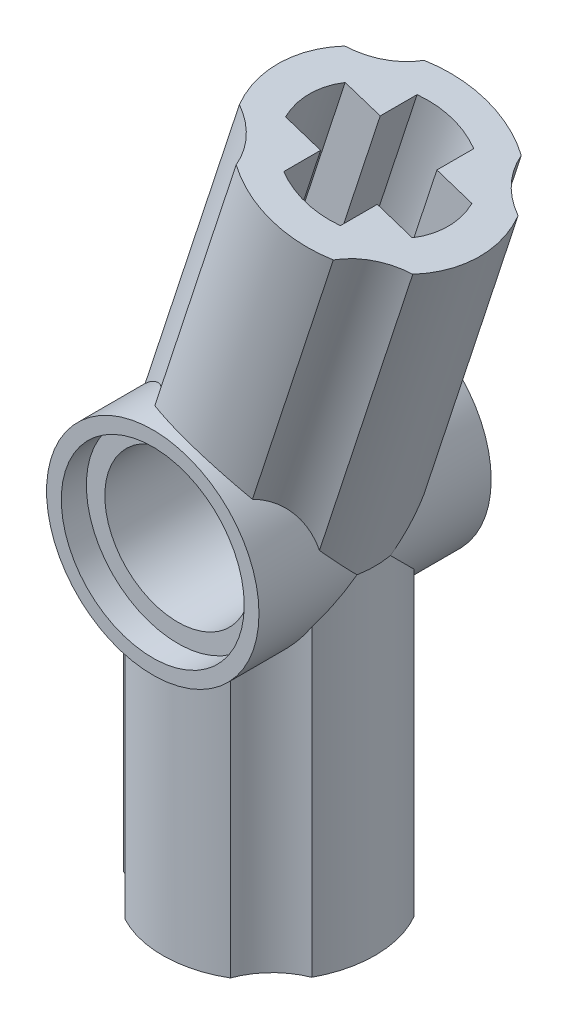
SolidWorks part; units mm, degrees
ref_plane "Front Plane" through (0, 0, 0) normal (0, 0, 1) x (1, 0, 0)
ref_plane "Top Plane" through (0, 0, 0) normal (0, 1, 0) x (1, 0, 0)
ref_plane "Right Plane" through (0, 0, 0) normal (1, 0, 0) x (0, 0, -1)
sketch "Croquis1" plane through (0, 0, 0) normal (0, 0, 1) x (1, 0, 0)
  circle A0 centre (0, 0) radius 3.1
  circle A1 centre (0, 0) radius 3.6
  circle A2 centre (0, 0) radius 2.475
  dimension "D1" = 4.95
  dimension "D2" = 6.2
  dimension "D3" = 7.2
extrude "Saliente-Extruir1" add sketch "Croquis1" along normal blind 7.87 contours A1 A0 region at (-3.4982, 0, 0)
extrude "Saliente-Extruir2" add sketch "Croquis1<3>" along normal offset from surface (6.17 mm away) 0.85 from offset 0.85 contours A0 A2 region at (-3.0123, 0, 0) up to face at (3.1, 0, 7.87)
sketch "Croquis1<3>" plane through (0, 0, 0) normal (0, 0, 1) x (1, 0, 0) same geometry as "Croquis1"
ref_plane "Plano1" through (0, -4, 0) normal (0, 1, 0) x (1, 0, 0)
sketch "Croquis2" plane through (0, -4, 0) normal (0, 1, 0) x (1, 0, 0)
  line L0 (-1.01, -6.1945) -> (-1.01, -4.945)
  line L1 (1.01, -6.1945) -> (1.01, -4.945)
  line L2 (-2.2595, -2.925) -> (-1.01, -2.925)
  line L3 (2.2595, -4.945) -> (1.01, -4.945)
  line L4 (-1.01, -4.945) -> (-2.2595, -4.945)
  line L5 (1.01, -2.925) -> (1.01, -1.6755)
  line L6 (-1.01, -2.925) -> (-1.01, -1.6755)
  line L7 (1.01, -2.925) -> (2.2595, -2.925)
  arc A0 (-1.01, -6.1945) -> (1.01, -6.1945) centre (0, -3.935) ccw
  arc A1 (-1.7125, -7.1016) -> (1.8067, -7.0488) centre (0, -3.935) ccw
  arc A2 (-1.7125, -7.1016) -> (-3.1138, -5.7417) centre (-3.94, -7.995) ccw
  arc A3 (-3.1666, -2.2225) -> (-1.8067, -0.8212) centre (-4.06, 0.005) ccw
  arc A4 (1.7125, -0.7684) -> (3.1138, -2.1283) centre (3.94, 0.125) ccw
  arc A5 (3.1666, -5.6475) -> (1.8067, -7.0488) centre (4.06, -7.875) ccw
  arc A6 (3.1666, -5.6475) -> (3.1138, -2.1283) centre (0, -3.935) ccw
  arc A7 (1.7125, -0.7684) -> (-1.8067, -0.8212) centre (0, -3.935) ccw
  arc A8 (-3.1666, -2.2225) -> (-3.1138, -5.7417) centre (0, -3.935) ccw
  arc A9 (2.2595, -4.945) -> (2.2595, -2.925) centre (0, -3.935) ccw
  arc A10 (1.01, -1.6755) -> (-1.01, -1.6755) centre (0, -3.935) ccw
  arc A11 (-2.2595, -2.925) -> (-2.2595, -4.945) centre (0, -3.935) ccw
  dimension "D2" = 4.95
  dimension "D3" = 7.2
  dimension "D4" = 4.8
  dimension "D1" = 3.935
  dimension "D5" = 3.94
  dimension "D6" = 4.06
  dimension "D8" = 2.02
  dimension "D9" = 1.01
  dimension "D10" = 2.02
  dimension "D11" = 1.01
  dimension "D7" = 4
extrude "Saliente-Extruir3" add sketch "Croquis2" along normal up to surface (0.8334 mm away) contours A3 A8 A2 A1 A5 A6 A4 A7 A11 L2 L6 A10 L5 L7 A9 L3 L1 A0 L0 L4 up to face at (3.6, 0, 7.87)
extrude "Saliente-Extruir4" add sketch "Croquis2<3>" against normal blind 8 contours A3 A8 A2 A1 A5 A6 A4 A7 A11 L2 L6 A10 L5 L7 A9 L3 L1 A0 L0 L4 region at (-2.1977, -4, 6.1996)
sketch "Croquis2<3>" plane through (0, -4, 0) normal (0, 1, 0) x (1, 0, 0) same geometry as "Croquis2"
sketch "Croquis5" plane through (0, 0, 0) normal (1, 0, 0) x (0, 0, -1)
  line L0 (0, 0) -> (-7.87, 0) construction
  line L1 (-7.87, 3.6) -> (-7.87, -3.6) construction
ref_plane "Plano3" through (0, 0, 0) normal (-0.3103, -0.9506, 0) x (0, 0, 1)
ref_plane "Plano4" through (1.2414, 3.8025, 0) normal (-0.3103, -0.9506, 0) x (0, 0, 1)
sketch "Croquis7" plane through (1.2414, 3.8025, 0) normal (-0.3103, -0.9506, 0) x (0, 0, 1)
  line L0 (2.925, -2.2595) -> (2.925, -1.01)
  line L1 (4.945, -2.2595) -> (4.945, -1.01)
  line L2 (1.6755, 1.01) -> (2.925, 1.01)
  line L3 (6.1945, -1.01) -> (4.945, -1.01)
  line L4 (2.925, -1.01) -> (1.6755, -1.01)
  line L5 (4.945, 1.01) -> (4.945, 2.2595)
  line L6 (2.925, 1.01) -> (2.925, 2.2595)
  line L7 (4.945, 1.01) -> (6.1945, 1.01)
  line L8 (7.87, -3.6) -> (7.87, 3.6) construction
  arc A0 (2.925, -2.2595) -> (4.945, -2.2595) centre (3.935, 0) ccw
  arc A1 (2.2225, -3.1666) -> (5.7417, -3.1138) centre (3.935, 0) ccw
  arc A2 (2.2225, -3.1666) -> (0.8212, -1.8067) centre (-0.005, -4.06) ccw
  arc A4 (5.6475, 3.1666) -> (7.0488, 1.8067) centre (7.875, 4.06) ccw
  arc A6 (7.1016, -1.7125) -> (7.0488, 1.8067) centre (3.935, 0) ccw
  arc A7 (5.6475, 3.1666) -> (2.1283, 3.1138) centre (3.935, 0) ccw
  arc A8 (0.7684, 1.7125) -> (0.8212, -1.8067) centre (3.935, 0) ccw
  arc A9 (6.1945, -1.01) -> (6.1945, 1.01) centre (3.935, 0) ccw
  arc A10 (4.945, 2.2595) -> (2.925, 2.2595) centre (3.935, 0) ccw
  arc A11 (1.6755, 1.01) -> (1.6755, -1.01) centre (3.935, 0) ccw
  arc A12 (7.1016, -1.7125) -> (5.7417, -3.1138) centre (7.995, -3.94) ccw
  arc A13 (2.2225, -3.1666) -> (0.8212, -1.8067) centre (-0.005, -4.06) ccw
  arc A14 (0.7684, 1.7125) -> (2.1283, 3.1138) centre (-0.125, 3.94) ccw
  dimension "D1" = 4.95
  dimension "D2" = 7.2
  dimension "D3" = 4.8
  dimension "D13" = 2.4
  dimension "D4" = 3.94
  dimension "D5" = 4.06
  dimension "D6" = 2.02
  dimension "D7" = 1.01
  dimension "D8" = 2.02
  dimension "D9" = 1.01
  dimension "D10" = 3.935
  dimension "D11" = 3.94
  dimension "D12" = 4.06
  dimension "D14" = 4
extrude "Saliente-Extruir5" add sketch "Croquis7" along normal up to surface (0.8334 mm away) contours A12 A1 A2 A8 A14 A7 A4 A6 up to face at (0, -2.0794, 3.935)
extrude "Saliente-Extruir6" add sketch "Croquis7<3>" against normal blind 8 contours A14 A8 A2 A1 A12 A6 A4 A7 A11 L2 L6 A10 L5 L7 A9 L3 L1 A0 L0 L4 region at (3.3942, 3.0997, 1.7373)
sketch "Croquis7<3>" plane through (1.2414, 3.8025, 0) normal (-0.3103, -0.9506, 0) x (0, 0, 1) same geometry as "Croquis7"
equation "\"D9@Croquis2\"=\"D8@Croquis2\"/2"
equation "\"D11@Croquis2\"=\"D10@Croquis2\"/2"
equation "\"angle\"= 163"
